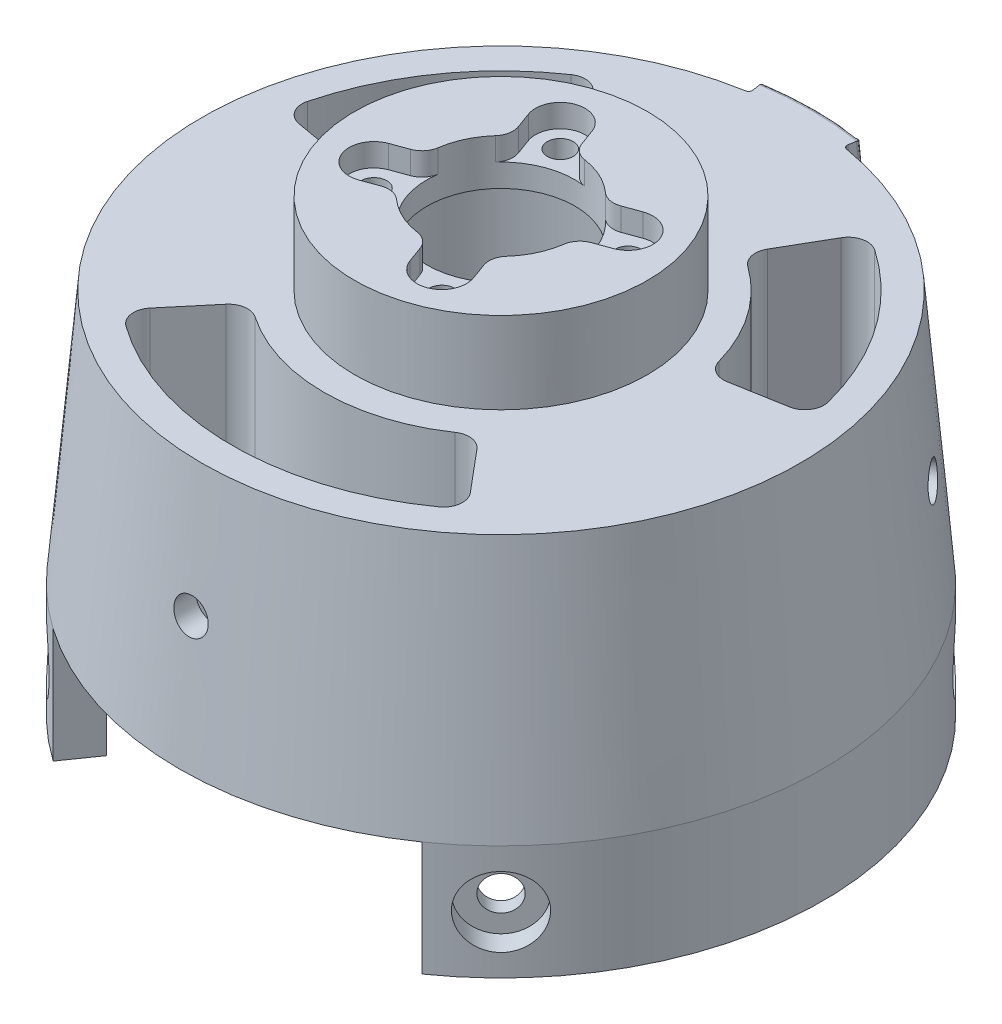
SolidWorks part; units mm, degrees
ref_plane "Front Plane" through (0, 0, 0) normal (0, 0, 1) x (1, 0, 0)
ref_plane "Top Plane" through (0, 0, 0) normal (0, 1, 0) x (1, 0, 0)
ref_plane "Right Plane" through (0, 0, 0) normal (1, 0, 0) x (0, 0, -1)
sketch "Sketch1" plane through (0, 0, 0) normal (0, 1, 0) x (1, 0, 0)
  line L0 (-29.85, 23.9174) -> (-29.85, -23.9174)
  line L1 (29.85, 23.9174) -> (29.85, -23.9174)
  line L2 (-29.85, 0) -> (29.85, 0) construction
  arc A0 (-29.85, -23.9174) -> (29.85, -23.9174) centre (0, 0) ccw
  arc A1 (29.85, 23.9174) -> (-29.85, 23.9174) centre (0, 0) ccw
  point P9 (0, 0)
  dimension "D1" = 59.7
  dimension "D2" = 76.5
extrude "Boss-Extrude1" add sketch "Sketch1" along normal blind 44
sketch "Sketch2" plane through (0, 44, 0) normal (0, 1, 0) x (1, 0, 0)
  line L0 (-4.4463, 12.216) -> (0, 0) construction
  line L1 (0, 13) -> (0, 0) construction
  circle A0 centre (0, 0) radius 13
  point P3 (-4.4463, 12.216)
  dimension "D1" = 26
  dimension "D2" = 20
hole_wizard "CBORE for M3 SHCS1" positions "Sketch2" profile "Sketch3" counterbore size "M3" standard "ANSI Metric" end condition through all
sketch "Sketch3" plane through (-4.4463, 44, -12.216) normal (1, 0, 0) x (0, 0, 1)
  line L0 (0, 0) -> (0, 44)
  line L1 (0, 44) -> (1.7, 44)
  line L3 (1.7, 44) -> (1.7, 3)
  line L4 (1.7, 3) -> (3.25, 3)
  line L5 (3.25, 3) -> (3.25, 0)
  line L7 (3.25, 0) -> (0, 0)
  line L11 (0, -6.35) -> (0, 107.95) construction
  dimension "Thru Hole Dia." = 3.4
  dimension "Thru Hole Depth" = 44
  dimension "C'Bore Dia." = 6.5
  dimension "C'Bore Depth" = 3
ref_axis "Axis1" through (0, 44, 0) along (0, -1, 0)
pattern_circular "CirPattern1" count 4 over 360 about axis through (0, 44, 0) along (0, -1, 0) of "CBORE for M3 SHCS1"
sketch "Sketch4" plane through (0, 0, 0) normal (0, -1, 0) x (1, 0, 0)
  circle A0 centre (0, 0) radius 16.2
  dimension "D1" = 32.4
extrude "Cut-Extrude1" cut sketch "Sketch4" against normal blind 38
sketch "Sketch5" plane through (0, 44, 0) normal (0, 1, 0) x (1, 0, 0)
  circle A0 centre (0, 0) radius 9.7
extrude "Cut-Extrude2" cut sketch "Sketch5" against normal through all
ref_plane "Plane1" through (0, 0, -38.25) normal (0, 0, -1) x (-1, 0, 0)
sketch "Sketch7" plane through (0, 0, 0) normal (0, -1, 0) x (1, 0, 0)
  line L5 (29.85, 23.9174) -> (29.85, -23.9174)
  line L6 (-29.85, 23.9174) -> (-29.85, -23.9174)
  arc A0 (-29.85, -23.9174) -> (29.85, -23.9174) centre (0, 0) ccw construction
  arc A1 (29.85, 23.9174) -> (-29.85, 23.9174) centre (0, 0) ccw construction
  arc A2 (-29.85, -23.9174) -> (29.85, -23.9174) centre (0, 0) ccw
  arc A3 (29.85, 23.9174) -> (-29.85, 23.9174) centre (0, 0) ccw
  circle A4 centre (0, 0) radius 42.1622
  dimension "D1" = 84.3245
extrude "Boss-Extrude2" add sketch "Sketch7" against normal up to surface (44 mm away) up to face at (0, 44, 9.7)
sketch "Sketch9" plane through (0, 0, 0) normal (1, 0, 0) x (0, 0, -1)
  line L0 (-42.1622, 0) -> (-38.3127, 44)
  line L1 (-38.3127, 44) -> (-42.1622, 44)
  line L2 (-42.1622, 44) -> (-42.1622, 0) construction
  line L3 (-42.1622, 44) -> (-42.1622, 0)
  line L4 (0, 0) -> (0, 44) construction
  line L5 (42.1622, 44) -> (-42.1622, 44) construction
  dimension "D1" = 5
revolve "Cut-Revolve2" cut sketch "Sketch9" angle 360 about L4
sketch "Sketch10" plane through (0, 0, 0) normal (1, 0, 0) x (0, 0, -1)
  line L0 (-19.2, 44) -> (-19.2, 33.2871)
  line L1 (38.3127, 44) -> (-38.3127, 44) construction
  line L2 (-19.2, 33.2871) -> (-39.25, 33.2871)
  line L3 (-38.3127, 44) -> (-42.1622, 0) construction
  line L4 (-39.25, 33.2871) -> (-38.3127, 44)
  line L5 (-38.3127, 44) -> (-19.2, 44)
  line L6 (0, 0) -> (0, 44) construction
  line L10 (-42.1622, 0) -> (42.1622, 0) construction
  line L11 (-16.2, 0) -> (16.2, 0) construction
  line L12 (-16.2, 0) -> (16.2, 0) construction
  line L13 (38.3127, 44) -> (-38.3127, 44) construction
  dimension "D1" = 10.7129
  dimension "D2" = 33.2871
  dimension "D3" = 3
revolve "Cut-Revolve3" cut sketch "Sketch10" angle 360 about L6
sketch "Sketch13" plane through (0, 33.2871, 0) normal (0, 1, 0) x (1, 0, 0)
  line L0 (0, -35.25) -> (0, -39.25) construction
  circle A0 centre (0, 0) radius 35.25
  circle A1 centre (0, 0) radius 19.2 construction
  circle A2 centre (0, 0) radius 19.2
  circle A3 centre (0, 0) radius 39.25 construction
  dimension "D1" = 4
extrude "Cut-Extrude3" cut sketch "Sketch13" against normal through all both and the other way through all
sketch "Sketch16" plane through (0, 0, 0) normal (0, -1, 0) x (1, 0, 0)
  line L0 (0, -35.25) -> (0, -19.2) construction
  line L1 (-17.625, -30.5274) -> (-9.6, -16.6277)
  line L2 (17.625, -30.5274) -> (9.6, -16.6277)
  line L3 (-34.7145, -6.1211) -> (-18.9083, -3.334)
  line L4 (-22.6583, 27.0031) -> (-12.3415, 14.7081)
  line L5 (22.6583, 27.0031) -> (12.3415, 14.7081)
  line L6 (34.7145, -6.1211) -> (18.9083, -3.334)
  line L7 (0, 0) -> (-33.1242, 12.0562) construction
  circle A1 centre (0, 0) radius 35.25 construction
  circle A2 centre (0, 0) radius 19.2 construction
  arc A3 (-9.6, -16.6277) -> (9.6, -16.6277) centre (0, 0) ccw
  arc A4 (-17.625, -30.5274) -> (17.625, -30.5274) centre (0, 0) ccw
  arc A5 (-22.6583, 27.0031) -> (-34.7145, -6.1211) centre (0, 0) ccw
  arc A6 (-12.3415, 14.7081) -> (-18.9083, -3.334) centre (0, 0) ccw
  arc A7 (22.6583, 27.0031) -> (34.7145, -6.1211) centre (0, 0) cw
  arc A8 (12.3415, 14.7081) -> (18.9083, -3.334) centre (0, 0) cw
  point P19 (0, 0)
  dimension "D1" = 16.05
  dimension "D3" = 60
  dimension "D4" = 110
  dimension "D2" = 2
extrude "Boss-Extrude4" add sketch "Sketch16" against normal up to surface (33.2871 mm away) up to face at (0, 33.2871, 35.25)
sketch "Sketch17" plane through (0, 33.2871, 0) normal (0, 1, 0) x (1, 0, 0)
  line L0 (0, -19.2) -> (0, -23.2) construction
  circle A0 centre (0, 0) radius 23.2
  circle A1 centre (0, 0) radius 19.2 construction
  circle A2 centre (0, 0) radius 19.2
  dimension "D1" = 4
extrude "Boss-Extrude5" add sketch "Sketch17" against normal up to surface (33.2871 mm away) up to face at (-21.2567, 0, -14.8841)
fillet "Fillet2" radius 2.5 12 edges at (-14.9127, 16.6435, 17.7722) (-22.6583, 16.6435, 27.0031) (22.6583, 16.6435, 27.0031) (14.9127, 16.6435, 17.7722) (-17.625, 16.6435, -30.5274) (-34.7145, 16.6435, -6.1211) (-22.8475, 16.6435, -4.0286) (-11.6, 16.6435, -20.0918) (34.7145, 16.6435, -6.1211) (17.625, 16.6435, -30.5274) (11.6, 16.6435, -20.0918) (22.8475, 16.6435, -4.0286)
ref_plane "Plane2" through (0, 16.6435, 0) normal (0, -1, 0) x (-1, 0, 0)
sketch "Sketch18" plane through (0, 16.6435, 0) normal (0, -1, 0) x (-1, 0, 0)
  line L0 (0, 0) -> (28.8751, 20.2186) construction
  line L1 (0, 0) -> (-28.8751, 20.2186) construction
  line L2 (0, 0) -> (0, -35.25) construction
  line L3 (0, 0) -> (-10.7822, -33.5605) construction
  line L4 (0, 0) -> (10.7822, -33.5605) construction
  arc A0 (34.1459, 8.7532) -> (19.9039, 29.0929) centre (0, 0) ccw construction
  arc A1 (-19.9039, 29.0929) -> (-34.1459, 8.7532) centre (0, 0) ccw construction
  arc A2 (-20.5308, -28.6539) -> (20.5308, -28.6539) centre (0, 0) ccw construction
  arc A3 (-20.5308, -28.6539) -> (0, -35.25) centre (0, 0) ccw construction
  arc A4 (0, -35.25) -> (20.5308, -28.6539) centre (0, 0) ccw construction
ref_plane "Plane4" through (-28.8751, 16.6435, -20.2186) normal (-0.8192, 0, -0.5736) x (-0.5736, 0, 0.8192)
sketch "Sketch20" plane through (-28.8751, 16.6435, -20.2186) normal (-0.8192, 0, -0.5736) x (-0.5736, 0, 0.8192)
  circle A0 centre (0, 0) radius 2.25
  dimension "D1" = 4.5
extrude "Cut-Extrude5" cut sketch "Sketch20" against normal blind 10 and the other way through all
sketch "Sketch21" plane through (-28.8751, 16.6435, -20.2186) normal (-0.8192, 0, -0.5736) x (-0.5736, 0, 0.8192)
  line L1 (4.0415, 0) -> (2.0207, 3.5)
  line L2 (2.0207, 3.5) -> (-2.0207, 3.5)
  line L3 (-2.0207, 3.5) -> (-4.0415, 0)
  line L4 (-4.0415, 0) -> (-2.0207, -3.5)
  line L5 (-2.0207, -3.5) -> (2.0207, -3.5)
  line L6 (2.0207, -3.5) -> (4.0415, 0)
  circle A0 centre (0, 0) radius 3.5 construction
  dimension "D1" = 4.0415
  dimension "D2" = 7
extrude "Cut-Extrude6" cut sketch "Sketch21" against normal blind 10 and the other way blind 2.5
pattern_circular "CirPattern2" count 3 over 250 about axis through (0, 0, 0) along (0, 1, 0) of "Cut-Extrude5", "Cut-Extrude6"
sketch "Sketch22" plane through (0, 44, 0) normal (0, 1, 0) x (1, 0, 0)
  line L2 (-12.216, -4.4463) -> (12.216, 4.4463) construction
  line L3 (-13.3276, -1.3923) -> (11.1044, 7.5003) construction
  line L4 (-11.1044, -7.5003) -> (13.3276, 1.3923) construction
  line L5 (-4.4463, 12.216) -> (4.4463, -12.216) construction
  line L6 (-1.3923, 13.3276) -> (7.5003, -11.1044) construction
  line L7 (-7.5003, 11.1044) -> (1.3923, -13.3276) construction
  line L8 (-11.1044, -7.5003) -> (-1.9424, -4.1656)
  line L9 (-1.9424, -4.1656) -> (1.3923, -13.3276)
  line L10 (7.5003, -11.1044) -> (4.1656, -1.9424)
  line L11 (4.1656, -1.9424) -> (13.3276, 1.3923)
  line L12 (11.1044, 7.5003) -> (1.9424, 4.1656)
  line L13 (1.9424, 4.1656) -> (-1.3923, 13.3276)
  line L14 (-7.5003, 11.1044) -> (-4.1656, 1.9424)
  line L15 (-4.1656, 1.9424) -> (-13.3276, -1.3923)
  arc A0 (-13.3276, -1.3923) -> (-11.1044, -7.5003) centre (-12.216, -4.4463) ccw
  arc A1 (1.3923, -13.3276) -> (7.5003, -11.1044) centre (4.4463, -12.216) ccw
  arc A2 (13.3276, 1.3923) -> (11.1044, 7.5003) centre (12.216, 4.4463) ccw
  arc A3 (-1.3923, 13.3276) -> (-7.5003, 11.1044) centre (-4.4463, 12.216) ccw
  arc A10 (-13.3276, -1.3923) -> (-11.1044, -7.5003) centre (-12.216, -4.4463) ccw construction
  arc A11 (13.3276, 1.3923) -> (11.1044, 7.5003) centre (12.216, 4.4463) ccw construction
  circle A12 centre (12.216, 4.4463) radius 3.25 construction
  arc A13 (-1.3923, 13.3276) -> (-7.5003, 11.1044) centre (-4.4463, 12.216) ccw construction
  arc A14 (1.3923, -13.3276) -> (7.5003, -11.1044) centre (4.4463, -12.216) ccw construction
  circle A15 centre (4.4463, -12.216) radius 3.25 construction
  point P2 (0, 0)
  point P11 (0, 0)
extrude "temporary_probnably" cut sketch "Sketch22" against normal up to surface (3 mm away) up to face at (-4.4463, 41, -10.516)
fillet "also_probably_temporary" radius 2.5 8 edges at (-9.6997, 42.5, 0.0718) (-7.4766, 42.5, 6.1798) (0.0718, 42.5, 9.6997) (6.1798, 42.5, 7.4766) (9.6997, 42.5, -0.0718) (7.4766, 42.5, -6.1798) (-0.0718, 42.5, -9.6997) (-6.1798, 42.5, -7.4766)
sketch "Sketch24" plane through (0, 0, 0) normal (1, 0, 0) x (0, 0, -1)
  line L0 (39.25, 33.2871) -> (-39.25, 33.2871) construction
  line L1 (-42.1622, 0) -> (42.1622, 0) construction
  line L2 (39.25, 33.2871) -> (-39.25, 33.2871) construction
  line L3 (-42.1622, 0) -> (42.1622, 0) construction
  line L4 (42.1622, 0) -> (44.1622, 0)
  line L5 (39.25, 33.2871) -> (41.25, 33.2871)
  line L6 (39.25, 33.2871) -> (42.1622, 0)
  line L7 (41.25, 33.2871) -> (44.1622, 0)
  line L8 (0, 33.2871) -> (0, 0) construction
  dimension "D1" = 2
revolve "key_1" add sketch "Sketch24" angle 9 about L8 other way angle 9
fillet "key_2" radius 0.5 6 edges at (0, 0, -44.1622) (0, 33.2871, -41.25) (-6.6807, 16.6435, -42.1803) (6.6807, 16.6435, -42.1803) (-6.3678, 16.6435, -40.205) (6.3678, 16.6435, -40.205)
sketch "Sketch25" plane through (0, 0, 0) normal (0, -1, 0) x (1, 0, 0)
  line L0 (-24.1833, -34.5373) -> (24.1833, 34.5373) construction
  line L1 (24.1833, -34.5373) -> (-24.1833, 34.5373) construction
  line L2 (-21.3154, 30.4415) -> (-24.1833, 34.5373)
  line L3 (-21.3154, -30.4415) -> (-24.1833, -34.5373)
  line L4 (0, 0) -> (0, 42.1622) construction
  line L6 (21.3154, 30.4415) -> (24.1833, 34.5373)
  line L7 (21.3154, -30.4415) -> (24.1833, -34.5373)
  arc A1 (-24.1833, 34.5373) -> (-24.1833, -34.5373) centre (0, 0) ccw
  circle A3 centre (0, 0) radius 37.1622 construction
  arc A4 (7.0833, -41.563) -> (-7.0833, -41.563) centre (0, 0) ccw construction
  arc A7 (-21.3154, -30.4415) -> (-21.3154, 30.4415) centre (0, 0) cw
  arc A20 (7.0833, -41.563) -> (-7.0833, -41.563) centre (0, 0) ccw construction
  arc A21 (21.3154, -30.4415) -> (21.3154, 30.4415) centre (0, 0) ccw
  arc A22 (24.1833, 34.5373) -> (24.1833, -34.5373) centre (0, 0) cw
  point P14 (0, 37.1622)
  point P16 (0, 37.1622)
  dimension "D1" = 70
  dimension "D2" = 5
extrude "Boss-Extrude6" add sketch "Sketch25" along normal blind 15
ref_plane "Plane5" through (0, -7.5, 0) normal (0, -1, 0) x (-1, 0, 0)
sketch "Sketch26" plane through (0, -7.5, 0) normal (0, -1, 0) x (-1, 0, 0)
  line L0 (0, 0) -> (42.1622, 0) construction
  line L1 (0, 0) -> (29.8132, -29.8132) construction
  arc A0 (24.1833, -34.5373) -> (24.1833, 34.5373) centre (0, 0) ccw construction
  dimension "D1" = 45
ref_plane "Plane6" through (-29.8132, -7.5, 29.8132) normal (-0.7071, 0, 0.7071) x (0.7071, 0, 0.7071)
sketch "Sketch28" plane through (-29.8132, -7.5, 29.8132) normal (-0.7071, 0, 0.7071) x (0.7071, 0, 0.7071)
  circle A0 centre (0, 0) radius 2.25
  dimension "D1" = 4.5
extrude "Cut-Extrude7" cut sketch "Sketch28" along normal through all and the other way up to surface other way up to face at (29.2388, -7.5, 0)
sketch "Sketch29" plane through (-29.8132, -7.5, 29.8132) normal (-0.7071, 0, 0.7071) x (0.7071, 0, 0.7071)
  circle A0 centre (0, 0) radius 2.25 construction
  circle A1 centre (0, 0) radius 2.25
  circle A2 centre (0, 0) radius 4.6
  dimension "D1" = 9.2
extrude "Cut-Extrude8" cut sketch "Sketch29" against normal blind 3
mirror "Mirror1" about plane through (0, 0, 0) normal (0, 0, 1) of "Cut-Extrude8", "Cut-Extrude7"
mirror "Mirror2" about plane through (0, 0, 0) normal (1, 0, 0) of "Mirror1"
